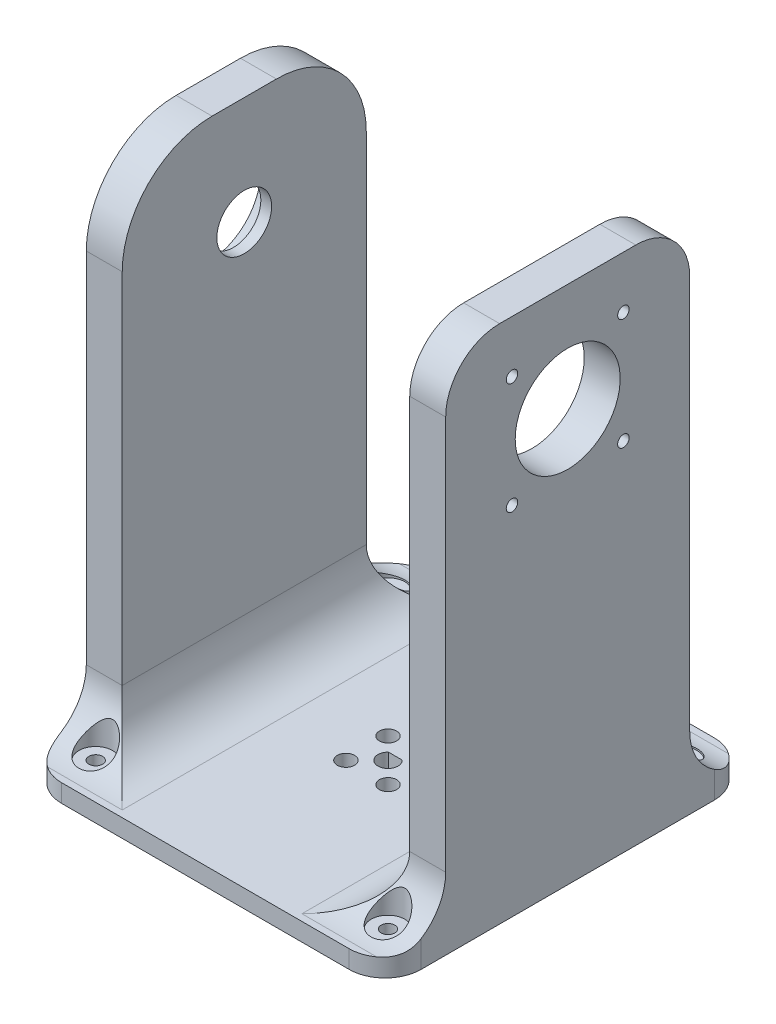
SolidWorks part; units mm, degrees
ref_plane "Front Plane" through (0, 0, 0) normal (0, 0, 1) x (1, 0, 0)
ref_plane "Top Plane" through (0, 0, 0) normal (0, 1, 0) x (1, 0, 0)
ref_plane "Right Plane" through (0, 0, 0) normal (1, 0, 0) x (0, 0, -1)
sketch "Sketch2" plane through (0, 0, 0) normal (0, 1, 0) x (1, 0, 0)
  line L1 (-50, 50.8) -> (50, 50.8)
  line L2 (-50, 50.8) -> (-50, -50.8)
  line L3 (-50, -50.8) -> (50, -50.8)
  line L4 (50, 50.8) -> (50, -50.8)
  line L5 (-50, 50.8) -> (50, -50.8) construction
  line L6 (-50, -50.8) -> (50, 50.8) construction
  line L7 (-50, 50.8) -> (-40, 50.8)
  line L8 (-50, 50.8) -> (-50, -50.8)
  line L9 (-50, -50.8) -> (-40, -50.8)
  line L10 (-40, 50.8) -> (-40, -50.8)
  line L11 (50, 50.8) -> (40, 50.8)
  line L12 (50, 50.8) -> (50, -50.8)
  line L13 (50, -50.8) -> (40, -50.8)
  line L14 (40, 50.8) -> (40, -50.8)
  point P0 (0, 0)
  dimension "D1" = 101.6
  dimension "D2" = 100
  dimension "D3" = 10
  dimension "D4" = 10
extrude "Boss-Extrude1" add sketch "Sketch2" along normal blind 139.7 contours L10 L1 L2 L3 | L1 L14 L3 L4 region at (-45, 0, 0) region at (45, 0, 0)
extrude "Boss-Extrude2" add sketch "Sketch2<3>" against normal blind 5 contours L1 L14 L3 L4 | L14 L1 L10 L3 | L10 L1 L2 L3 region at (-45, 0, 0) region at (0, 0, 0) region at (45, 0, 0)
sketch "Sketch2<3>" plane through (0, 0, 0) normal (0, 1, 0) x (1, 0, 0) same geometry as "Sketch2"
sketch "Sketch3" plane through (-50, 0, 0) normal (-1, 0, 0) x (0, 0, 1)
  line L0 (0, 139.7) -> (0, -5) construction
  line L1 (-50.8, 139.7) -> (50.8, 139.7) construction
  line L2 (-50.8, -5) -> (50.8, -5) construction
  circle A0 centre (0, 109.7) radius 14.605
  dimension "D1" = 29.21
  dimension "D2" = 30
extrude "Cut-Extrude1" cut sketch "Sketch3" against normal blind 117
sketch "Sketch4" plane through (50, 0, 0) normal (1, 0, 0) x (0, 0, -1)
  line L0 (-33.9482, 139.7) -> (-33.9482, 0)
  line L1 (50.8, 139.7) -> (-50.8, 139.7) construction
  line L2 (-33.9482, 0) -> (-50.8, 0)
  line L3 (-50.8, -5) -> (-50.8, 139.7) construction
  line L4 (0, 139.7) -> (0, -5) construction
  line L5 (50.8, -5) -> (-50.8, -5) construction
  line L6 (33.9482, 0) -> (50.8, 0)
  line L7 (33.9482, 139.7) -> (33.9482, 0)
  line L8 (-33.9482, 139.7) -> (-50.8, 139.7)
  line L9 (-50.8, 139.7) -> (-50.8, 0)
  line L10 (33.9482, 139.7) -> (50.8, 139.7)
  line L11 (50.8, 139.7) -> (50.8, 0)
  dimension "D1" = 0
extrude "Cut-Extrude2" cut sketch "Sketch4" against normal blind 119
fillet "Fillet14" radius 15 8 edges at (40, 0, 0) (-40, 0, 0) (-45, 0, -33.9482) (-45, 0, 33.9482) (45, 0, 33.9482) (45, 0, -33.9482) (45, 139.7, 33.9482) (45, 139.7, -33.9482)
sketch "Sketch5" plane through (0, 0, 0) normal (0, 1, 0) x (1, 0, 0)
  line L1 (-1.9177, 2.032) -> (1.9177, 2.032)
  arc A0 (-1.9177, 2.032) -> (1.9177, 2.032) centre (0, 0) ccw
  dimension "D1" = 5.588
  dimension "D2" = 2.032
fillet "Fillet2" radius 10 4 edges at (50, -2.5, -50.8) (-50, -2.5, -50.8) (50, -2.5, 50.8) (-50, -2.5, 50.8)
sketch "Sketch7" plane through (50, 0, 0) normal (1, 0, 0) x (0, 0, -1)
  line L0 (0, 205.8998) -> (0, 13.5002) construction
  line L1 (-24.405, 109.7) -> (24.405, 109.7) construction
  circle A0 centre (-15.5, 125.2) radius 1.6
  circle A1 centre (15.5, 125.2) radius 1.6
  circle A2 centre (15.5, 94.2) radius 1.6
  circle A3 centre (-15.5, 94.2) radius 1.6
  point P5 (0, 109.7)
  point P8 (0, 109.7)
  dimension "D1" = 3.2
  dimension "D2" = 15.5
  dimension "D3" = 15.5
extrude "Cut-Extrude4" cut sketch "Sketch7" against normal blind 21
sketch "Sketch8" plane through (40, 0, 0) normal (-1, 0, 0) x (0, 0, 1)
  circle A0 centre (0, 109.7) radius 14.7541
  circle A1 centre (0, 109.7) radius 7.62
  dimension "D1" = 15.24
extrude "Boss-Extrude3" add sketch "Sketch8" along normal blind 3 from surface starting at face at (-40, 77.35, 0)
sketch "Sketch9" plane through (0, -5, 0) normal (0, -1, 0) x (1, 0, 0)
  line L0 (0, 50.8) -> (0, -50.8) construction
  line L2 (-40, -50.8) -> (40, -50.8) construction
  line L3 (-50, 0) -> (50, 0) construction
  line L5 (50, -40.8) -> (50, 40.8) construction
  circle A0 centre (-40.66, 40.66) radius 1.905
  circle A1 centre (40.66, 40.66) radius 1.905
  circle A2 centre (-40.66, -40.66) radius 1.905
  circle A3 centre (40.66, -40.66) radius 1.905
  point P4 (0, 0)
  point P10 (0, 0)
  dimension "D1" = 3.81
  dimension "D2" = 40.66
  dimension "D3" = 40.66
extrude "Cut-Extrude5" cut sketch "Sketch9" against normal through all
extrude "Cut-Extrude6" cut sketch "Sketch5" against normal blind 10
fillet "Fillet4" radius 25 2 edges at (-45, 139.7, -33.9482) (-45, 139.7, 33.9482)
sketch "Sketch10" plane through (0, 0, 0) normal (0, 1, 0) x (1, 0, 0)
  line L0 (-5.8563, 5.8563) -> (5.8563, 5.8563) construction
  line L1 (-5.8563, -5.8563) -> (5.8563, -5.8563) construction
  line L2 (-5.8563, 5.8563) -> (-5.8563, -5.8563) construction
  line L3 (0, 5.8563) -> (0, -5.8563) construction
  circle A0 centre (-5.8563, 5.8563) radius 2.4003
  circle A1 centre (5.8563, 5.8563) radius 2.4003
  circle A2 centre (-5.8563, -5.8563) radius 2.4003
  circle A3 centre (5.8563, -5.8563) radius 2.4003
  point P8 (0, 0)
  dimension "D1" = 4.8006
  dimension "D2" = 4.8006
  dimension "D3" = 4.8006
  dimension "D4" = 4.8006
  dimension "D5" = 11.7126
  dimension "D6" = 11.7126
  dimension "D7" = 11.7126
  dimension "D8" = 0
  dimension "D9" = 0
extrude "Cut-Extrude7" cut sketch "Sketch10" against normal blind 10
sketch "Sketch11" plane through (0, 0, 0) normal (0, 1, 0) x (1, 0, 0)
  circle A0 centre (-40.66, -40.66) radius 4.7
  circle A1 centre (40.66, -40.66) radius 4.7
  circle A2 centre (-40.66, 40.66) radius 4.7
  circle A3 centre (40.66, 40.66) radius 4.7
extrude "Cut-Extrude9" cut sketch "Sketch11" along normal blind 10
chamfer "Chamfer1" distance 1.778 angle 45 4 edges at (-40.66, -5, -38.755) (40.66, -5, -42.565) (40.66, -5, 42.565) (-40.66, -5, 38.755)
ref_plane "Plane1" through (40, 124.7, -33.9482) normal (0, -1, 0) x (-1, 0, 0)
sketch "Sketch12" plane through (40, 0, 0) normal (-1, 0, 0) x (0, 0, 1)
  circle A0 centre (-15.5, 125.2) radius 2.921
  circle A1 centre (15.5, 125.2) radius 2.921
  circle A2 centre (-15.5, 94.2) radius 2.921
  circle A3 centre (15.5, 94.2) radius 2.921
  dimension "D1" = 5.842
  dimension "D2" = 5.842
  dimension "D3" = 5.842
  dimension "D4" = 5.842
extrude "Cut-Extrude10" cut sketch "Sketch12" against normal blind 3.302
